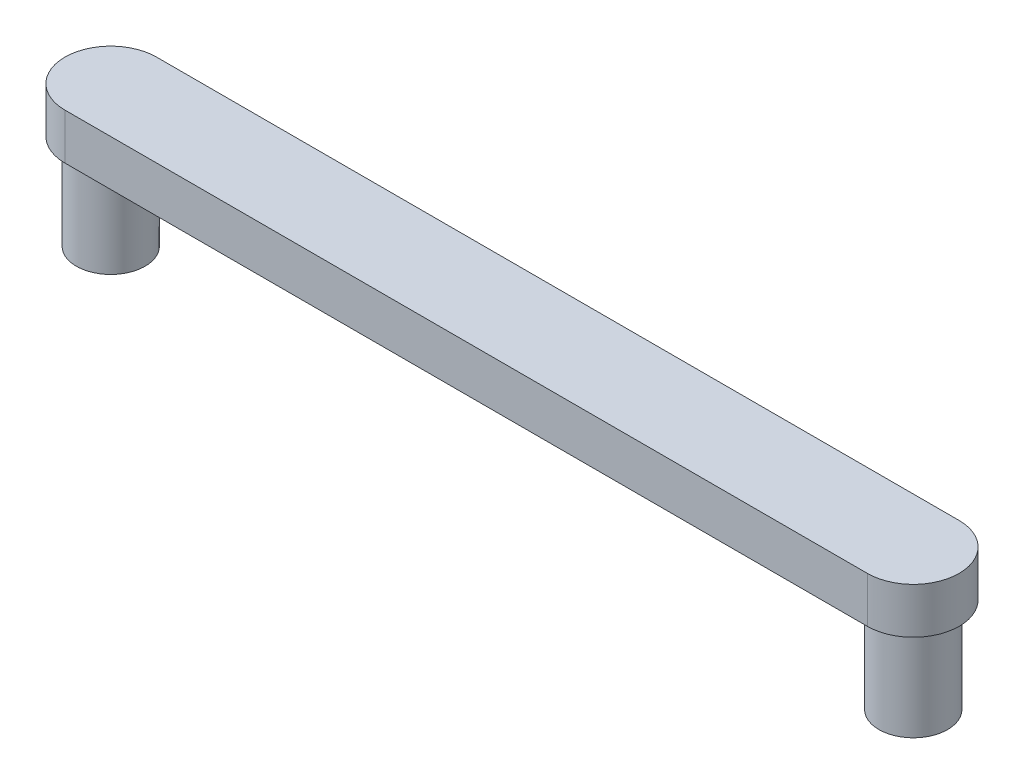
SolidWorks part; units mm, degrees
ref_plane "Front Plane" through (0, 0, 0) normal (0, 0, 1) x (1, 0, 0)
ref_plane "Top Plane" through (0, 0, 0) normal (0, 1, 0) x (1, 0, 0)
ref_plane "Right Plane" through (0, 0, 0) normal (1, 0, 0) x (0, 0, -1)
sketch "Sketch1" plane through (0, 0, 0) normal (0, 1, 0) x (1, 0, 0)
  circle A0 centre (0, 0) radius 1.5
  dimension "D1" = 3
extrude "Boss-Extrude1" add sketch "Sketch1" along normal blind 4.15
sketch "Sketch2" plane through (0, 4.15, 0) normal (0, 1, 0) x (1, 0, 0)
  line L0 (35, 0) -> (0, 0) construction
  line L1 (35, 2) -> (0, 2)
  line L2 (0, -2) -> (35, -2)
  line L3 (0, 2) -> (0, -2) construction
  arc A0 (0, 2) -> (0, -2) centre (0, 0) ccw
  arc A1 (35, -2) -> (35, 2) centre (35, 0) ccw
  dimension "D1" = 4
  dimension "D3" = 4
  dimension "D2" = 35
extrude "Boss-Extrude2" add sketch "Sketch2" along normal blind 2
sketch "Sketch3" plane through (0, 4.15, 0) normal (0, -1, 0) x (1, 0, 0)
  circle A0 centre (35, 0) radius 1.5
  dimension "D1" = 3
extrude "Boss-Extrude3" add sketch "Sketch3" along normal up to surface (4.15 mm away) up to face at (0, 0, 1.5)
